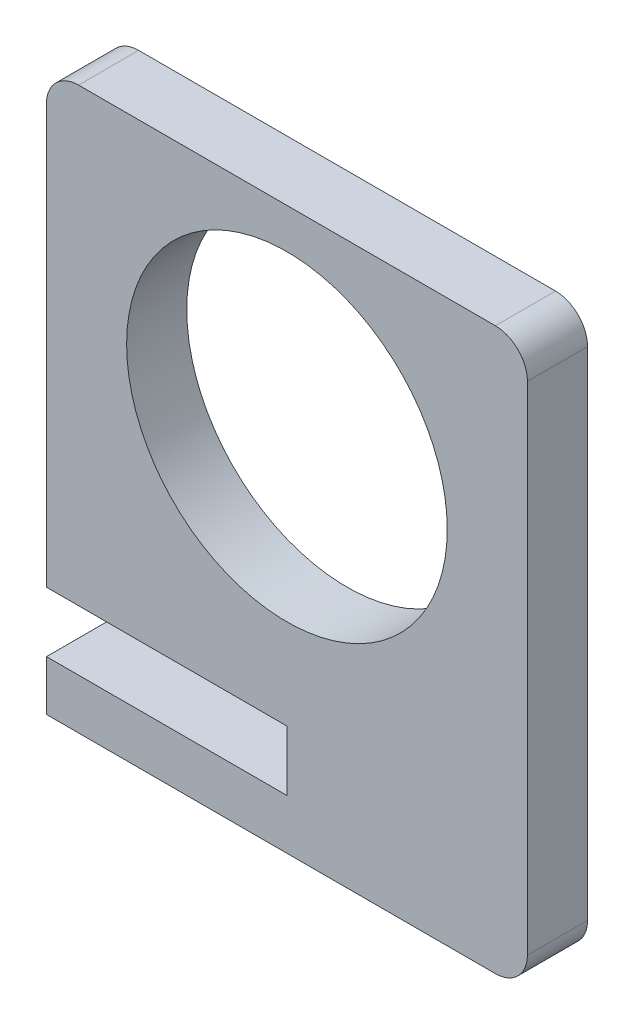
SolidWorks part; units mm, degrees
material "Corrugated Paper"
ref_plane "Front Plane" through (0, 0, 0) normal (0, 0, 1) x (1, 0, 0)
ref_plane "Top Plane" through (0, 0, 0) normal (0, 1, 0) x (1, 0, 0)
ref_plane "Right Plane" through (0, 0, 0) normal (1, 0, 0) x (0, 0, -1)
sketch "Sketch1" plane through (0, 0, 0) normal (0, 0, 1) x (1, 0, 0)
  line L0 (-19.05, 2.3813) -> (-19.05, 6.35)
  line L1 (-19.05, -2.3813) -> (0, -2.3813)
  line L3 (-19.05, 2.3813) -> (0, 2.3813)
  line L4 (0, -2.3813) -> (0, 2.3813)
  line L5 (-19.05, 6.35) -> (19.05, 6.35)
  line L6 (0, 0) -> (19.05, 0) construction
  line L7 (19.05, 6.35) -> (19.05, -6.35)
  line L8 (-19.05, -6.35) -> (19.05, -6.35)
  line L9 (-19.05, -2.3813) -> (-19.05, -6.35)
  line L10 (-19.05, 38.1) -> (19.05, 6.35) construction
  line L11 (-19.05, 6.35) -> (19.05, 6.35)
  line L12 (-19.05, 6.35) -> (-19.05, 38.1)
  line L13 (-19.05, 38.1) -> (19.05, 38.1)
  line L14 (19.05, 6.35) -> (19.05, 38.1)
  line L15 (19.05, 38.1) -> (-19.05, 6.35) construction
  circle A0 centre (0, 22.225) radius 12.7
  dimension "D6" = 25.4
  dimension "D1" = 19.05
  dimension "D2" = 4.7625
  dimension "D3" = 19.05
  dimension "D4" = 12.7
  dimension "D5" = 44.45
extrude "Boss-Extrude1" add sketch "Sketch1" along normal mid plane 4.7625 contours L5 L14 L13 L12 | L6 L4 L1 L9 L8 L7 | L4 L6 L7 L5 L0 L3 region at (2.1981, 0, 0) region at (-18.554, 22.225, 0)
fillet "Fillet1" radius 2.54 3 edges at (19.05, -6.35, 0) (-19.05, 38.1, 0) (19.05, 38.1, 0)
equation "\"D2@Sketch1\" = \"thick\""
equation "\"D1@Boss-Extrude1\"= \"thick\""
equation "\"rodThick\"= 0.1in"
equation "\"thick\"= 3/16in"
